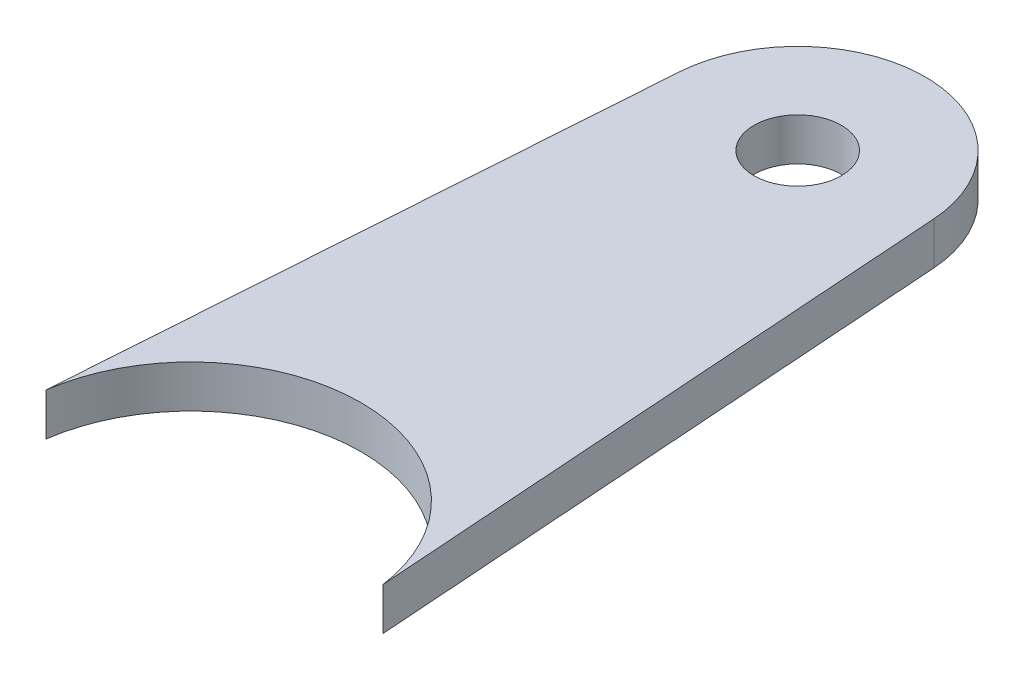
SolidWorks part; units mm, degrees
ref_plane "Front Plane" through (0, 0, 0) normal (0, 0, 1) x (1, 0, 0)
ref_plane "Top Plane" through (0, 0, 0) normal (0, 1, 0) x (1, 0, 0)
ref_plane "Right Plane" through (0, 0, 0) normal (1, 0, 0) x (0, 0, -1)
sketch "Sketch1" plane through (0, 0, 0) normal (0, 1, 0) x (1, 0, 0)
  line L0 (0, 0) -> (3.198, 45.9645)
  line L1 (0, 0) -> (25.4, 0)
  line L2 (25.4, 0) -> (22.202, 45.9645)
  arc A1 (3.198, 45.9645) -> (22.202, 45.9645) centre (12.7, 45.3034) cw
  circle A2 centre (12.7, 45.3034) radius 3.2639
  circle A3 centre (12.7, 0) radius 12.7
  point P9 (12.7, 0)
  dimension "D1" = 6.5278
  dimension "D2" = 45.3034
  dimension "D3" = 9.525
  dimension "D5" = 25.4
  dimension "D4" = 25.4
extrude "Boss-Extrude1" add sketch "Sketch1" along normal blind 3.175 contours A3 L2 A1 L0 A2 region at (12.7, 0, -29.9923)
